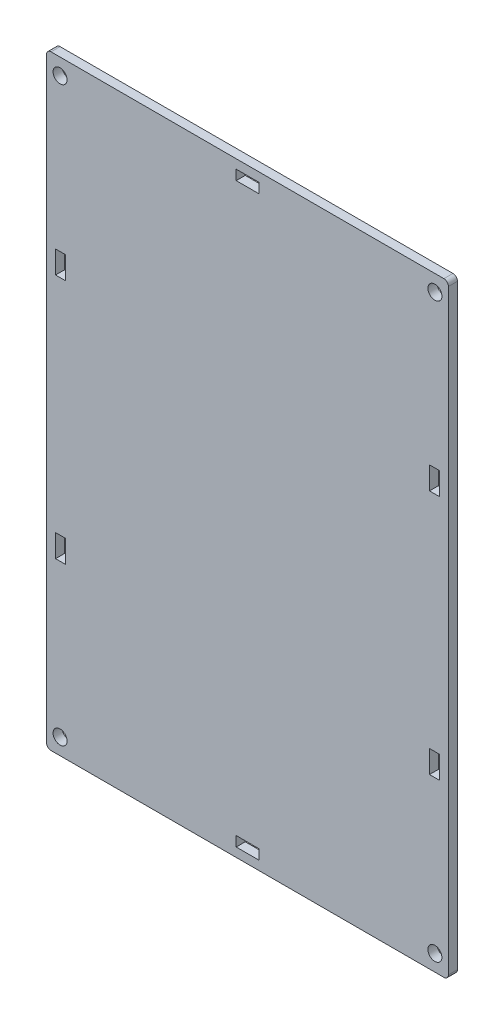
SolidWorks part; units mm, degrees
ref_plane "前基準面" through (0, 0, 0) normal (0, 0, 1) x (1, 0, 0)
ref_plane "上基準面" through (0, 0, 0) normal (0, 1, 0) x (1, 0, 0)
ref_plane "右基準面" through (0, 0, 0) normal (1, 0, 0) x (0, 0, -1)
sketch "Sketch1" plane through (0, 0, 0) normal (0, 0, 1) x (1, 0, 0)
  line L0 (0, 0) -> (-44.5, 0) construction
  line L1 (-44.5, 67) -> (44.5, 67)
  line L2 (-44.5, 67) -> (-44.5, -67)
  line L3 (-44.5, -67) -> (44.5, -67)
  line L4 (44.5, 67) -> (44.5, -67)
  line L5 (-44.5, 67) -> (44.5, -67) construction
  line L6 (-44.5, -67) -> (44.5, 67) construction
  line L7 (-44.5, 0) -> (44.5, 0) construction
  line L8 (0, 0) -> (0, -67) construction
  line L9 (0, -67) -> (0, 67) construction
  line L10 (-2.5, -62.8) -> (2.5, -62.8)
  line L11 (-2.5, 65) -> (2.5, 65)
  line L12 (-2.5, 65) -> (-2.5, 62.8)
  line L13 (-2.5, 62.8) -> (2.5, 62.8)
  line L14 (2.5, 65) -> (2.5, 62.8)
  line L15 (-2.5, 65) -> (2.5, 62.8) construction
  line L16 (-2.5, 62.8) -> (2.5, 65) construction
  line L17 (2.5, -65) -> (2.5, -62.8)
  line L18 (-2.5, -65) -> (2.5, -65)
  line L19 (-2.5, -65) -> (-2.5, -62.8)
  line L20 (-42.5, -24.7) -> (-40.3, -24.7)
  line L21 (-42.5, 29.7) -> (-40.3, 29.7)
  line L22 (-42.5, 29.7) -> (-42.5, 24.7)
  line L23 (-42.5, 24.7) -> (-40.3, 24.7)
  line L24 (-40.3, 29.7) -> (-40.3, 24.7)
  line L25 (-42.5, 29.7) -> (-40.3, 24.7) construction
  line L26 (-42.5, 24.7) -> (-40.3, 29.7) construction
  line L27 (-40.3, -29.7) -> (-40.3, -24.7)
  line L28 (-42.5, -29.7) -> (-40.3, -29.7)
  line L29 (-42.5, -29.7) -> (-42.5, -24.7)
  line L30 (42.5, -29.7) -> (42.5, -24.7)
  line L31 (42.5, -29.7) -> (40.3, -29.7)
  line L32 (40.3, -29.7) -> (40.3, -24.7)
  line L33 (42.5, -24.7) -> (40.3, -24.7)
  line L34 (42.5, 24.7) -> (40.3, 24.7)
  line L35 (40.3, 29.7) -> (40.3, 24.7)
  line L36 (42.5, 29.7) -> (40.3, 29.7)
  line L37 (42.5, 29.7) -> (42.5, 24.7)
  circle A0 centre (-41.5, 63.4) radius 1.55
  circle A1 centre (-41.5, -63.4) radius 1.55
  circle A2 centre (41.5, -63.4) radius 1.55
  circle A3 centre (41.5, 63.4) radius 1.55
  point P0 (0, 0)
  point P19 (0, 63.9)
  point P28 (-41.4, 27.2)
  dimension "D4" = 3.1
  dimension "D1" = 89
  dimension "D2" = 134
  dimension "D3" = 3.6
  dimension "D5" = 3
  dimension "D6" = 2
  dimension "D7" = 5
  dimension "D8" = 2.2
  dimension "D9" = 27.2
  dimension "D10" = 2
  dimension "D11" = 5
  dimension "D12" = 2.2
extrude "Boss-Extrude1" add sketch "Sketch1" along normal mid plane 2
fillet "Fillet1" radius 1 4 edges at (44.5, 67, 0) (44.5, -67, 0) (-44.5, -67, 0) (-44.5, 67, 0)
